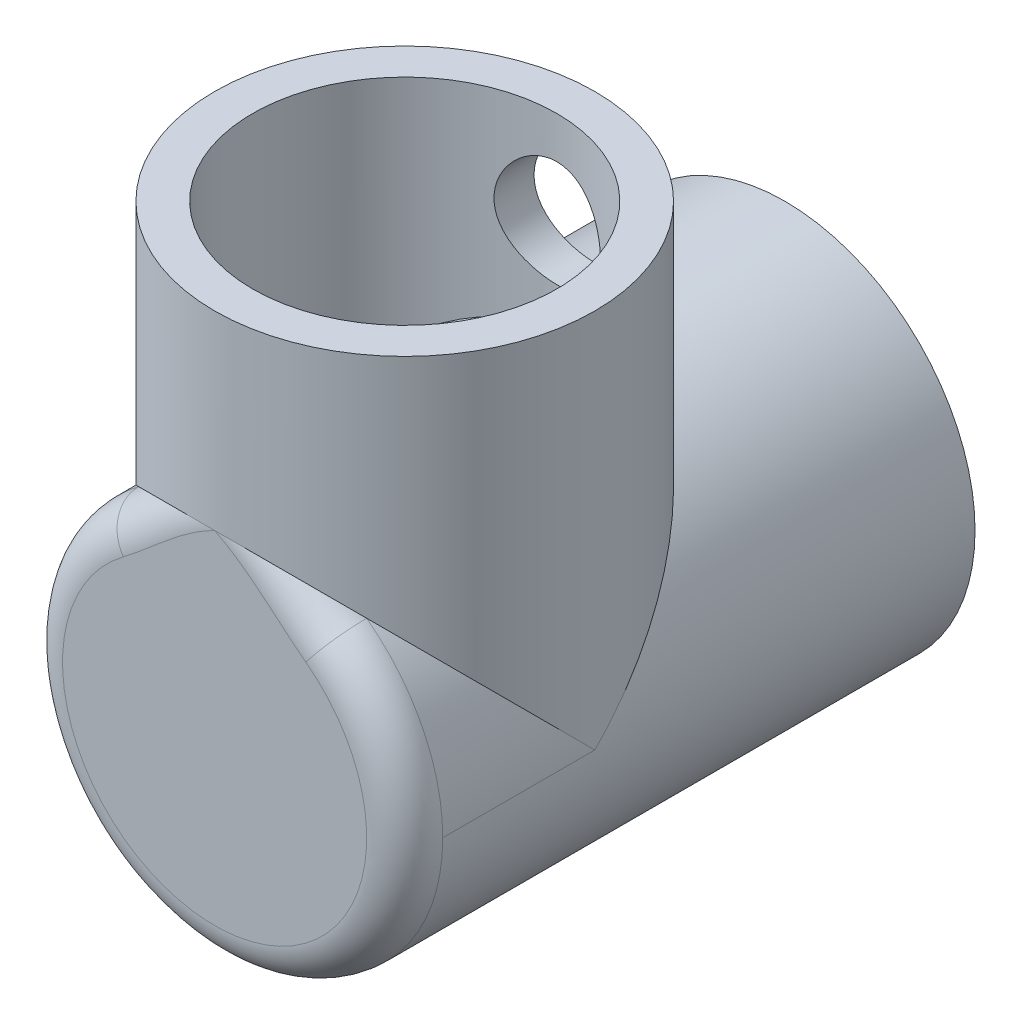
SolidWorks part; units mm, degrees
ref_plane "Alzado" through (0, 0, 0) normal (0, 0, 1) x (1, 0, 0)
ref_plane "Planta" through (0, 0, 0) normal (0, 1, 0) x (1, 0, 0)
ref_plane "Vista lateral" through (0, 0, 0) normal (1, 0, 0) x (0, 0, -1)
sketch "Croquis1" plane through (0, 0, 0) normal (0, 0, 1) x (1, 0, 0)
  circle A0 centre (0, 0) radius 1.5
  circle A1 centre (0, 0) radius 5
  dimension "D1" = 3
  dimension "D2" = 10
extrude "Saliente-Extruir1" add sketch "Croquis1" along normal blind 15
sketch "Croquis2" plane through (0, 0, 0) normal (0, 1, 0) x (1, 0, 0)
  line L0 (5, 0) -> (-5, 0) construction
  circle A0 centre (0, -4) radius 1.4
  dimension "D1" = 2.8
  dimension "D2" = 4
extrude "Cortar-Extruir1" cut sketch "Croquis2" against normal through all
sketch "Croquis3" plane through (0, 0, 0) normal (0, 1, 0) x (1, 0, 0)
  line L0 (-5, -15) -> (5, -15) construction
  circle A0 centre (0, -10) radius 4
  circle A1 centre (0, -10) radius 5
  dimension "D2" = 8
  dimension "D3" = 10
  dimension "D1" = 5
extrude "Saliente-Extruir2" add sketch "Croquis3" along normal blind 10
sketch "Croquis4" plane through (0, 0, 0) normal (0, 0, 1) x (1, 0, 0)
  line L0 (5, 10) -> (-5, 10) construction
  circle A0 centre (0, 7.5) radius 1.4
  dimension "D1" = 2.8
  dimension "D2" = 2.5
extrude "Cortar-Extruir2" cut sketch "Croquis4" along normal blind 10
fillet "Redondeo2" radius 1 1 edges at (5, 0, 15)
sketch "Croquis5" plane through (0, 0, 15) normal (0, 0, 1) x (1, 0, 0)
  circle A0 centre (0, 0) radius 1.5
extrude "Cortar-Extruir3" cut sketch "Croquis5" against normal blind 10
sketch "Croquis6" plane through (0, 0, 15) normal (0, 0, 1) x (1, 0, 0)
  circle A0 centre (0, 0) radius 1.5
extrude "Saliente-Extruir3" add sketch "Croquis6" against normal blind 3
